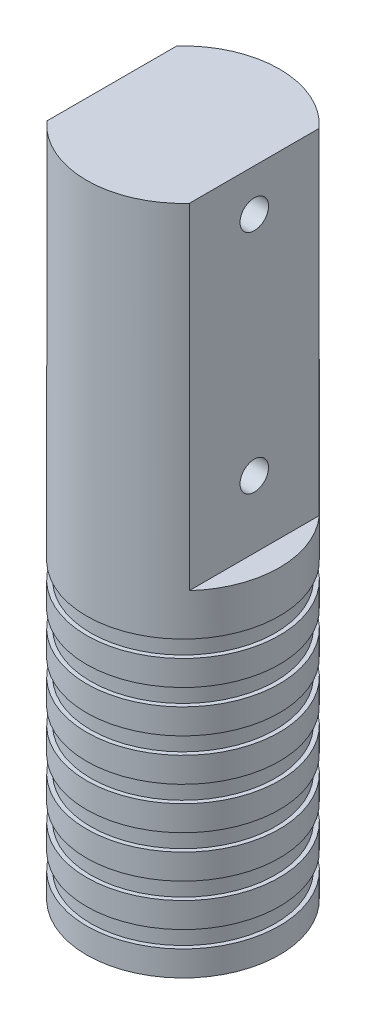
SolidWorks part; units mm, degrees
material "6061-T6 (SS)"
ref_plane "Front Plane" through (0, 0, 0) normal (0, 0, 1) x (1, 0, 0)
ref_plane "Top Plane" through (0, 0, 0) normal (0, 1, 0) x (1, 0, 0)
ref_plane "Right Plane" through (0, 0, 0) normal (1, 0, 0) x (0, 0, -1)
sketch "Sketch2" plane through (0, 0, 0) normal (0, 0, 1) x (1, 0, 0)
  line L0 (-11.5, 0) -> (11.5, 0)
  line L1 (11.5, 0) -> (11.5, -40)
  line L2 (11.5, -40) -> (0, -40)
  line L4 (0, 0) -> (0, -40)
  line L6 (-11.5, -40) -> (0, -40)
  line L7 (-11.5, 0) -> (-11.5, -40)
  point P4 (0, 0)
  dimension "D1" = 23
  dimension "D4" = 40
revolve "Revolve1" add sketch "Sketch2" angle 360 about L4 region at (-5.75, -20, 0)
sketch "Sketch3" plane through (0, 0, 0) normal (0, 0, 1) x (1, 0, 0)
  line L0 (-11.5, -40) -> (11.5, -40) construction
  line L1 (-11.5, -40) -> (11.5, -40)
  line L2 (11.5, -40) -> (11.5, -37)
  line L3 (11.5, -40) -> (11.5, 0) construction
  line L4 (11.5, -37) -> (11, -37)
  line L5 (11, -37) -> (11, -35)
  line L6 (11, -35) -> (11.5, -35)
  line L7 (11.5, -37) -> (11.5, -35)
  dimension "D1" = 2
  dimension "D2" = 0.5
  dimension "D3" = 3
revolve "Cut-Revolve1" cut sketch "Sketch3" angle 360 about L4
pattern_linear "LPattern1" count 7 spacing 5 along (0, 1, 0) of "Cut-Revolve1"
sketch "Sketch4" plane through (0, -40, 0) normal (0, -1, 0) x (1, 0, 0)
  point P0 (0, 0)
sketch "Sketch6" plane through (0, 0, 0) normal (0, 1, 0) x (1, 0, 0)
  line L0 (-8.5, 7.746) -> (-8.5, -7.746)
  line L2 (0, 0) -> (0, 11.5) construction
  line L3 (8.5, 7.746) -> (8.5, -7.746)
  line L4 (0, 0) -> (-8.5, 0) construction
  line L5 (-8.5, 1.5) -> (0, 1.5) construction
  arc A0 (8.5, 7.746) -> (-8.5, 7.746) centre (0, 0) ccw
  circle A1 centre (0, 0) radius 11.5 construction
  arc A2 (8.5, -7.746) -> (-8.5, -7.746) centre (0, 0) cw
  point P7 (-11.5, 0)
  dimension "D1" = 3
  dimension "D2" = 1.5
extrude "Boss-Extrude1" add sketch "Sketch6" along normal blind 40
hole_wizard "Ø15.0 (15) Diameter Hole1" positions "Sketch4" profile "Sketch5" hole size "Ø15.0" standard "ANSI Metric"
sketch "Sketch5" plane through (0, -40, 0) normal (1, 0, 0) x (0, 0, -1)
  line L0 (0, 0) -> (0, 44.5065)
  line L1 (0, 44.5065) -> (7.5, 40)
  line L2 (7.5, 40) -> (7.5, 0)
  line L5 (7.5, 0) -> (0, 0)
  line L10 (0, 44.5065) -> (-7.5, 40) construction
  line L11 (0, -6.35) -> (0, 107.95) construction
  dimension "Hole Dia." = 15
  dimension "Hole Depth" = 40
  dimension "Drill Angle" = 118
sketch "Sketch8" plane through (8.5, 0, 0) normal (1, 0, 0) x (0, 0, -1)
  line L2 (0, 8) -> (0, 35) construction
  line L3 (7.746, 0) -> (-7.746, 0) construction
  circle A0 centre (0, 8) radius 1.5 construction
  point P0 (0, 8)
  point P1 (0, 35)
  dimension "D1" = 3
  dimension "D2" = 8
  dimension "D3" = 27
hole_wizard "M3 Clearance Hole1" positions "Sketch8" profile "Sketch14" hole size "M3" standard "ANSI Metric" end condition through all
sketch "Sketch14" plane through (8.5, 8, 0) normal (0, 1, 0) x (0, 0, -1)
  line L0 (0, 0) -> (0, 20)
  line L1 (0, 20) -> (1.7, 20)
  line L2 (1.7, 20) -> (1.7, 0)
  line L5 (1.7, 0) -> (0, 0)
  line L11 (0, -6.35) -> (0, 107.95) construction
  dimension "Thru Hole Dia." = 3.4
  dimension "Thru Hole Depth" = 20
